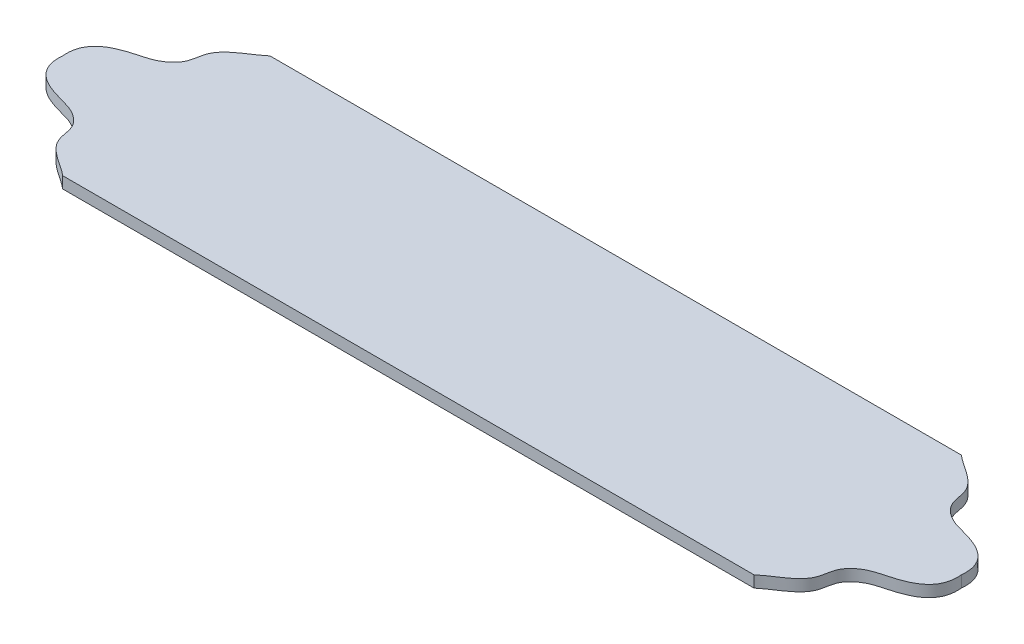
SolidWorks part; units mm, degrees
ref_plane "Front Plane" through (0, 0, 0) normal (0, 0, 1) x (1, 0, 0)
ref_plane "Top Plane" through (0, 0, 0) normal (0, 1, 0) x (1, 0, 0)
ref_plane "Right Plane" through (0, 0, 0) normal (1, 0, 0) x (0, 0, -1)
sketch "Sketch1" plane through (0, 0, 0) normal (0, 1, 0) x (1, 0, 0)
  line L0 (-495.3, 0) -> (495.3, 0) construction
  line L1 (-381, -114.3) -> (381, -114.3)
  line L3 (-381, 114.3) -> (381, 114.3)
  line L5 (-381, -114.3) -> (381, 114.3) construction
  line L6 (-381, 114.3) -> (381, -114.3) construction
  line L7 (0, -114.3) -> (0, 114.3) construction
  spline S0 degree 3 poles (-495.3, 0) (-497.9792, -25.8186) (-471.4197, -38.9822) (-438.3817, -45.8241) (-419.9559, -60.5175) (-419.4267, -93.4283) (-392.2969, -104.3239) (-381, -114.3) knots 0 0 0 0 0.342208 0.464465 0.60214 0.710952 1 1 1 1
  spline S1 degree 3 poles (-495.3, 0) (-497.9792, 25.8186) (-471.4197, 38.9822) (-438.3817, 45.8241) (-419.9559, 60.5175) (-419.4267, 93.4283) (-392.2969, 104.3239) (-381, 114.3) knots 0 0 0 0 0.342208 0.464465 0.60214 0.710952 1 1 1 1
  spline S2 degree 3 poles (495.3, 0) (497.9792, 25.8186) (471.4197, 38.9822) (438.3817, 45.8241) (419.9559, 60.5175) (419.4267, 93.4283) (392.2969, 104.3239) (381, 114.3) knots 0 0 0 0 0.342208 0.464465 0.60214 0.710952 1 1 1 1
  spline S3 degree 3 poles (495.3, 0) (497.9792, -25.8186) (471.4197, -38.9822) (438.3817, -45.8241) (419.9559, -60.5175) (419.4267, -93.4283) (392.2969, -104.3239) (381, -114.3) knots 0 0 0 0 0.342208 0.464465 0.60214 0.710952 1 1 1 1
  point P0 (0, 0)
  dimension "D1" = 762
  dimension "D2" = 228.6
  dimension "D3" = 990.6
extrude "Boss-Extrude1" add sketch "Sketch1" along normal blind 12.7
